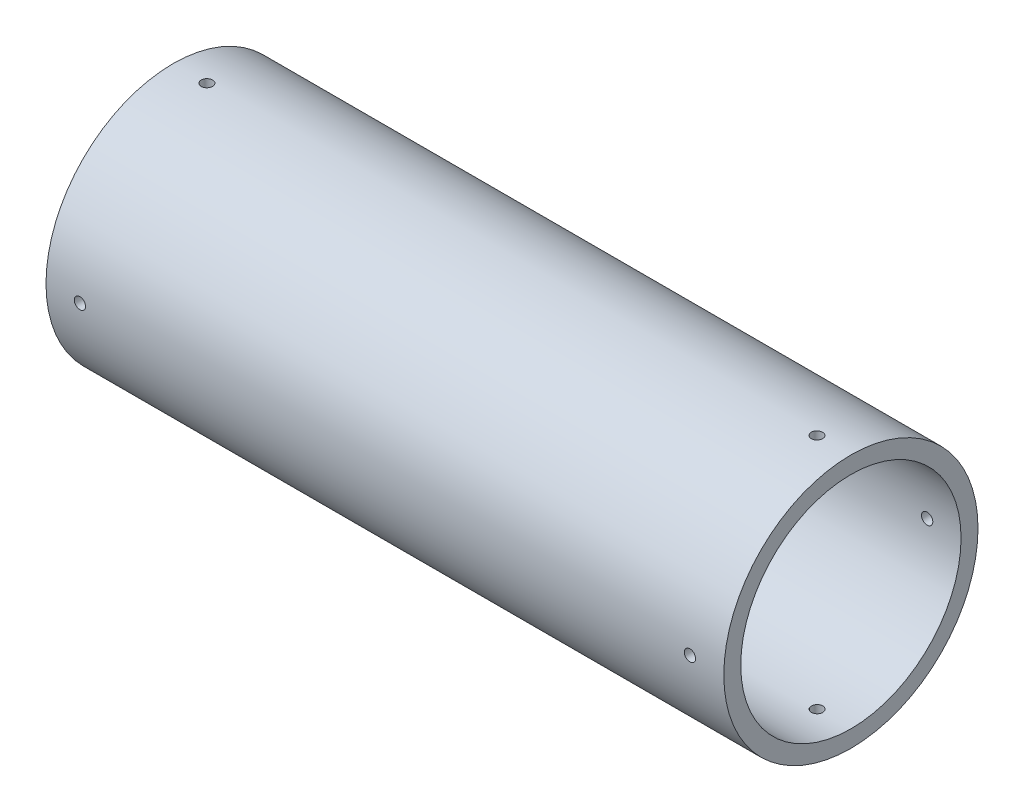
SolidWorks part; units mm, degrees
ref_plane "Спереди" through (0, 0, 0) normal (0, 0, 1) x (1, 0, 0)
ref_plane "Сверху" through (0, 0, 0) normal (0, 1, 0) x (1, 0, 0)
ref_plane "Справа" through (0, 0, 0) normal (1, 0, 0) x (0, 0, -1)
sketch "Эскиз1" plane through (0, 0, 0) normal (1, 0, 0) x (0, 0, -1)
  circle A0 centre (0, 0) radius 22.5
  circle A1 centre (0, 0) radius 19.5
  dimension "D1" = 45
  dimension "D2" = 39
extrude "Бобышка-Вытянуть1" add sketch "Эскиз1" along normal blind 120
sketch "Эскиз2" plane through (120, 0, 0) normal (1, 0, 0) x (0, 0, -1)
  line L0 (0, 22.5) -> (0, -22.5) construction
  circle A0 centre (0, 0) radius 22.5 construction
ref_plane "Плоскость1" through (0, 22.5, 0) normal (0, 1, 0) x (1, 0, 0)
sketch "Эскиз3" plane through (0, 22.5, 0) normal (0, 1, 0) x (1, 0, 0)
  line L0 (60, 22.5) -> (60, -22.5) construction
  line L1 (120, 22.5) -> (0, 22.5) construction
  line L2 (0, -22.5) -> (120, -22.5) construction
  line L3 (0, 0) -> (120, 0) construction
  line L4 (120, -22.5) -> (120, 22.5) construction
  circle A0 centre (6, 0) radius 1
  circle A1 centre (114, 0) radius 1
  dimension "D1" = 2
  dimension "D3" = 2
  dimension "D2" = 6
  dimension "D4" = 6
extrude "Вырез-Вытянуть1" cut sketch "Эскиз3" against normal blind 10
pattern_circular "Круговой массив1" count 4 over 360 about axis through (120, 0, 0) along (-1, 0, 0) of "Вырез-Вытянуть1" reverse direction yes
